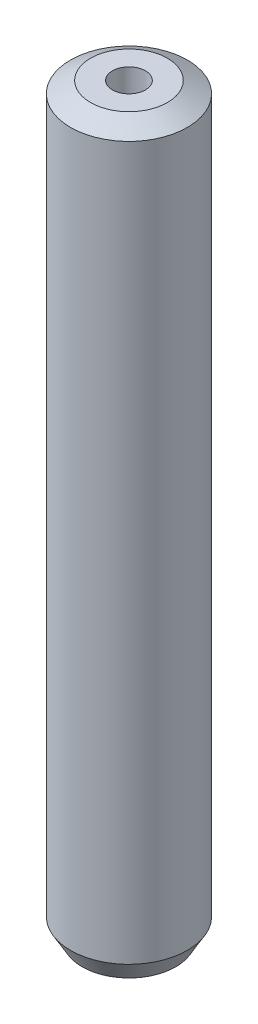
SolidWorks part; units mm, degrees
ref_plane "Front Plane" through (0, 0, 0) normal (0, 0, 1) x (1, 0, 0)
ref_plane "Top Plane" through (0, 0, 0) normal (0, 1, 0) x (1, 0, 0)
ref_plane "Right Plane" through (0, 0, 0) normal (1, 0, 0) x (0, 0, -1)
sketch "Sketch1" plane through (0, 0, 0) normal (0, 1, 0) x (1, 0, 0)
  circle A0 centre (0, 0) radius 15
  dimension "SHAFT_OD" = 30
extrude "Boss-Extrude1" add sketch "Sketch1" along normal blind 191.0433
sketch "Sketch2" plane through (0, 0, 0) normal (0, 1, 0) x (1, 0, 0)
  circle A0 centre (0, 0) radius 4.2458
  dimension "BORE_D" = 8.4916
extrude "Cut-Extrude1" cut sketch "Sketch2" along normal through all
chamfer "Chamfer1" distance 2.9659 angle 60 2 edges at (0, 191.0433, 15) (0, 0, 15) first distance on face at (0, 191.0433, 15) first distance on face at (0, 0, 4.2458)
